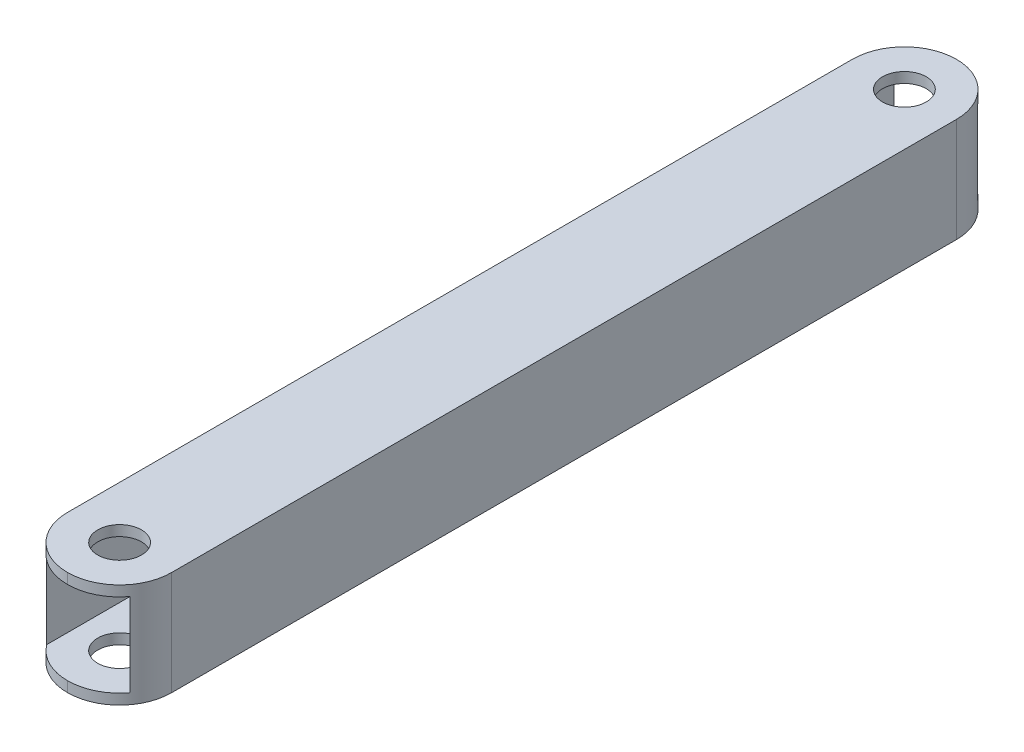
SolidWorks part; units mm, degrees
ref_plane "正面" through (0, 0, 0) normal (0, 0, 1) x (1, 0, 0)
ref_plane "平面" through (0, 0, 0) normal (0, 1, 0) x (1, 0, 0)
ref_plane "右側面" through (0, 0, 0) normal (1, 0, 0) x (0, 0, -1)
sketch "ｽｹｯﾁ1" plane through (0, 0, 0) normal (0, 0, 1) x (1, 0, 0)
  line L0 (-4, 4) -> (-4, -4)
  line L1 (-5, 5) -> (5, 5)
  line L2 (-5, 5) -> (-5, -5)
  line L3 (-5, -5) -> (5, -5)
  line L4 (5, 5) -> (5, -5)
  line L5 (-5, 5) -> (5, -5) construction
  line L6 (-5, -5) -> (5, 5) construction
  line L7 (-4, -4) -> (4, -4)
  line L8 (4, 4) -> (4, -4)
  line L9 (-4, 4) -> (4, 4)
  point P0 (0, 0)
  dimension "D1" = 10
  dimension "D2" = 10
  dimension "D3" = 1
extrude "ﾎﾞｽ - 押し出し1" add sketch "ｽｹｯﾁ1" along normal blind 85.3741
sketch "ｽｹｯﾁ2" plane through (0, 5, 0) normal (0, 1, 0) x (1, 0, 0)
  line L0 (5, 0) -> (-5, 0) construction
  line L1 (5, -85.3741) -> (-5, -85.3741) construction
  circle A0 centre (0, -5) radius 2.1
  circle A1 centre (0, -80.3741) radius 2.1
  dimension "D1" = 5
  dimension "D2" = 4.2
  dimension "D3" = 5
  dimension "D4" = 4.2
extrude "ｶｯﾄ - 押し出し1" cut sketch "ｽｹｯﾁ2" against normal blind 40
fillet "ﾌｨﾚｯﾄ1" radius 5 4 edges at (5, 0, 85.3741) (-5, 0, 85.3741) (5, 0, 0) (-5, 0, 0)
